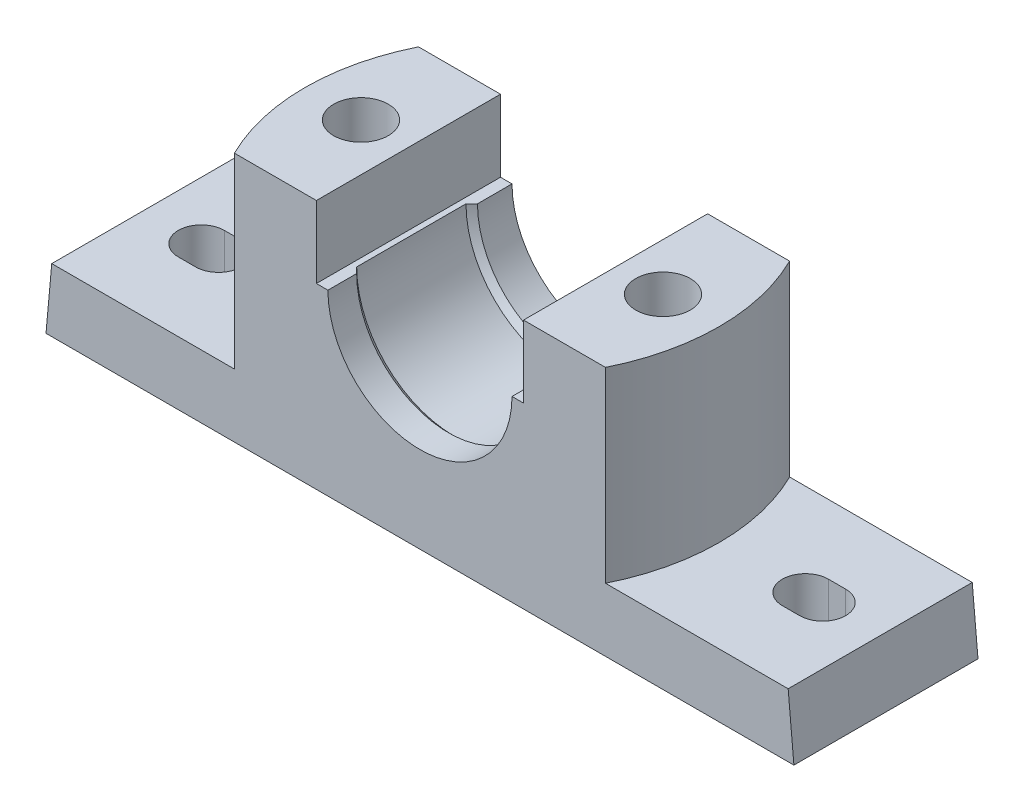
SolidWorks part; units mm, degrees
ref_plane "Front Plane" through (0, 0, 0) normal (0, 0, 1) x (1, 0, 0)
ref_plane "Top Plane" through (0, 0, 0) normal (0, 1, 0) x (1, 0, 0)
ref_plane "Right Plane" through (0, 0, 0) normal (1, 0, 0) x (0, 0, -1)
sketch "Sketch1" plane through (0, 0, 0) normal (0, 1, 0) x (1, 0, 0)
  line L1 (-130, -32) -> (130, -32)
  line L2 (-130, -32) -> (-130, 32)
  line L3 (-130, 32) -> (130, 32)
  line L4 (130, -32) -> (130, 32)
  point P0 (0, 0)
  dimension "D1" = 64
  dimension "D2" = 260
extrude "Boss-Extrude1" add sketch "Sketch1" along normal mid plane 22
sketch "Sketch2" plane through (0, 11, 0) normal (0, 1, 0) x (1, 0, 0)
  line L2 (108, 0) -> (102, 0) construction
  line L3 (-108, 0) -> (-102, 0) construction
  line L4 (-108, 8) -> (-102, 8)
  line L5 (-108, -8) -> (-102, -8)
  line L6 (108, 8) -> (102, 8)
  line L7 (108, -8) -> (102, -8)
  arc A0 (-108, 8) -> (-108, -8) centre (-108, 0) ccw
  arc A1 (-102, -8) -> (-102, 8) centre (-102, 0) ccw
  arc A2 (108, 8) -> (108, -8) centre (108, 0) cw
  arc A3 (102, -8) -> (102, 8) centre (102, 0) cw
  point P5 (-105, 0)
  point P8 (-105, 0)
  point P13 (105, 0)
  dimension "D1" = 16
  dimension "D3" = 25
  dimension "D4" = 25
  dimension "D5" = 16
extrude "Cut-Extrude1" cut sketch "Sketch2" against normal blind 22
sketch "Sketch3" plane through (0, 11, 0) normal (0, 1, 0) x (1, 0, 0)
  line L0 (-64.4981, 32) -> (64.4981, 32)
  line L1 (130, 32) -> (-130, 32) construction
  line L2 (-64.4981, -32) -> (64.4981, -32)
  line L3 (-130, -32) -> (130, -32) construction
  arc A0 (-64.4981, 32) -> (-64.4981, -32) centre (0, 0) ccw
  arc A1 (64.4981, -32) -> (64.4981, 32) centre (0, 0) ccw
  dimension "D1" = 144
extrude "Boss-Extrude2" add sketch "Sketch3" along normal blind 65
sketch "Sketch4" plane through (0, 0, 32) normal (0, 0, 1) x (1, 0, 0)
  line L0 (-130, 11) -> (-128, 11)
  line L1 (-130, 11) -> (-64.4981, 11) construction
  line L2 (-130, 11) -> (-130, -11)
  line L3 (-130, -11) -> (-128, 11)
  line L5 (130, -11) -> (128, 11)
  line L6 (130, 11) -> (128, 11)
  line L7 (130, 11) -> (130, -11)
extrude "Cut-Extrude2" cut sketch "Sketch4" against normal through all
sketch "Sketch5" plane through (0, 0, 32) normal (0, 0, 1) x (1, 0, 0)
  line L0 (-36, 76) -> (-19.975, 76)
  line L1 (-64.4981, 76) -> (64.4981, 76) construction
  line L2 (-19.975, 76) -> (36, 76)
  line L3 (-32, 51) -> (-36, 51)
  line L4 (32, 51) -> (36, 51)
  line L5 (-36, 76) -> (-36, 51)
  line L6 (36, 76) -> (36, 51)
  line L7 (-36, 76) -> (36, 76)
  arc A0 (-32, 51) -> (32, 51) centre (0, 51) ccw
  point P5 (0, 76)
  line M6 (64.4981, 76) -> (-64.4981, 76)
  dimension "D1" = 32
extrude "Cut-Extrude3" cut sketch "Sketch5" against normal blind 96 contours L3 A0 L4 L6 L5 M6 region at (0, 51.1921, 32)
sketch "Sketch6" plane through (0, 76, 0) normal (0, 1, 0) x (1, 0, 0)
  circle A0 centre (-52.5, 0) radius 9.5
  circle A1 centre (52.5, 0) radius 9.5
  dimension "D1" = 9.5
extrude "Cut-Extrude4" cut sketch "Sketch6" against normal blind 96
sketch "Sketch7" plane through (0, -11, 0) normal (0, -1, 0) x (1, 0, 0)
  circle A0 centre (-52.5, 0) radius 15
  circle A1 centre (52.5, 0) radius 15
  dimension "D1" = 15
  dimension "D2" = 15
extrude "Cut-Extrude5" cut sketch "Sketch7" against normal blind 12
sketch "Sketch10" plane through (0, 0, 32) normal (0, 0, 1) x (1, 0, 0)
  line L0 (-34, 51) -> (34, 51)
  arc A0 (-34, 51) -> (34, 51) centre (0, 51) ccw
  dimension "D1" = 34
extrude "Cut-Extrude7" cut sketch "Sketch10" against normal blind 38 from offset 12 contours L0 A0 offset against normal yes
chamfer "Chamfer1" distance 2 angle 45 1 edges at (0, 19, 20)
chamfer "Chamfer2" distance 2 angle 45 1 edges at (0, 19, -18)
sketch "Sketch13" plane through (0, -11, 0) normal (0, -1, 0) x (1, 0, 0)
  line L2 (-118, -20) -> (-4, -20)
  line L3 (-118, -20) -> (-118, 20)
  line L4 (-118, 20) -> (-4, 20)
  line L5 (-4, -20) -> (-4, 20)
  line L6 (118, -20) -> (118, 20)
  line L7 (118, -20) -> (4, -20)
  line L8 (4, -20) -> (4, 20)
  line L9 (118, 20) -> (4, 20)
  dimension "D3" = 40
  dimension "D4" = 114
extrude "Cut-Extrude8" cut sketch "Sketch13" against normal blind 2
